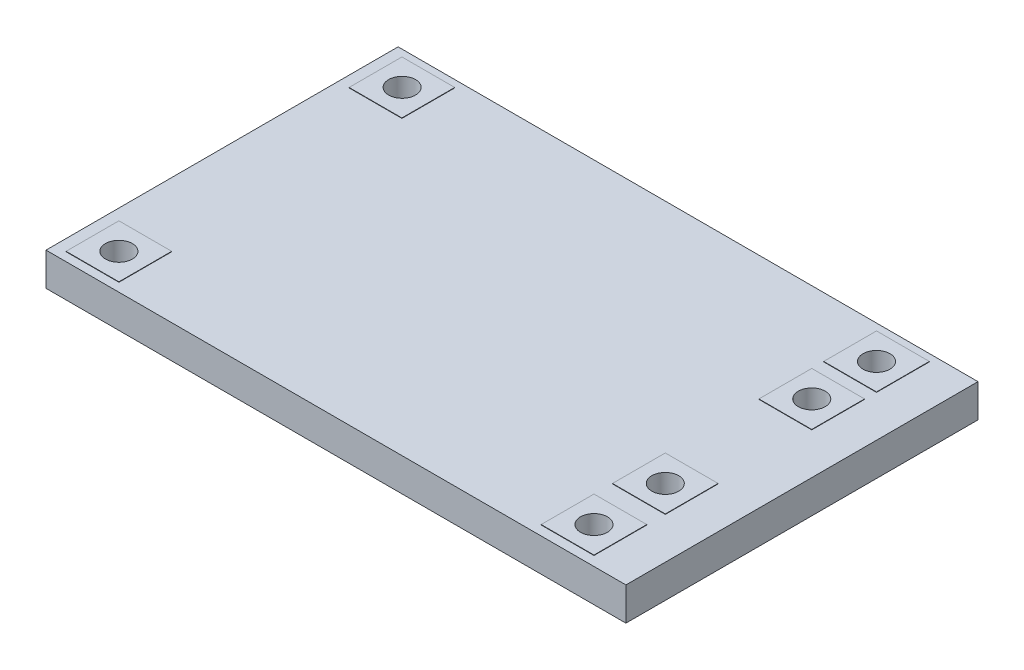
SolidWorks part; units mm, degrees
ref_plane "Front Plane" through (0, 0, 0) normal (0, 0, 1) x (1, 0, 0)
ref_plane "Top Plane" through (0, 0, 0) normal (0, 1, 0) x (1, 0, 0)
ref_plane "Right Plane" through (0, 0, 0) normal (1, 0, 0) x (0, 0, -1)
sketch "Sketch1" plane through (0, 0, 0) normal (0, 1, 0) x (1, 0, 0)
  line L0 (113.0265, 236.9079) -> (141.0265, 236.9079) construction
  line L1 (136.3804, 236.6517) -> (138.9304, 236.6517)
  line L2 (112.9304, 220.0017) -> (140.9304, 220.0017)
  line L3 (112.9304, 220.0017) -> (112.9304, 237.0017)
  line L4 (112.9304, 237.0017) -> (140.9304, 237.0017)
  line L5 (140.9304, 220.0017) -> (140.9304, 237.0017)
  line L6 (113.466, 236.6505) -> (116.016, 236.6505)
  line L7 (113.466, 236.6505) -> (113.466, 234.1005)
  line L8 (113.466, 234.1005) -> (116.016, 234.1005)
  line L9 (116.016, 236.6505) -> (116.016, 234.1005)
  line L10 (136.3804, 236.6517) -> (136.3804, 234.1017)
  line L11 (136.3804, 234.1017) -> (138.9304, 234.1017)
  line L12 (138.9304, 236.6517) -> (138.9304, 234.1017)
  line L13 (136.3846, 233.5201) -> (138.9346, 233.5201)
  line L14 (136.3846, 233.5201) -> (136.3846, 230.9701)
  line L15 (136.3846, 230.9701) -> (138.9346, 230.9701)
  line L16 (138.9346, 233.5201) -> (138.9346, 230.9701)
  line L17 (136.3832, 226.4506) -> (138.9332, 226.4506)
  line L18 (136.3832, 226.4506) -> (136.3832, 223.9006)
  line L19 (136.3832, 223.9006) -> (138.9332, 223.9006)
  line L20 (138.9332, 226.4506) -> (138.9332, 223.9006)
  line L21 (136.3796, 223.0107) -> (138.9296, 223.0107)
  line L22 (136.3796, 223.0107) -> (136.3796, 220.4607)
  line L23 (136.3796, 220.4607) -> (138.9296, 220.4607)
  line L24 (138.9296, 223.0107) -> (138.9296, 220.4607)
  line L25 (113.4856, 222.9666) -> (116.0356, 222.9666)
  line L26 (113.4856, 222.9666) -> (113.4856, 220.4166)
  line L27 (113.4856, 220.4166) -> (116.0356, 220.4166)
  line L28 (116.0356, 222.9666) -> (116.0356, 220.4166)
  circle A0 centre (114.741, 235.3847) radius 0.65
  circle A1 centre (137.6554, 235.3767) radius 0.65
  circle A2 centre (137.6596, 232.2451) radius 0.65
  circle A3 centre (137.6582, 225.1756) radius 0.65
  circle A4 centre (137.6546, 221.7357) radius 0.65
  circle A5 centre (114.7606, 221.6916) radius 0.65
  point P12 (0, 0)
  dimension "D6" = 1.3
  dimension "D7" = 1.275
  dimension "D1" = 28
  dimension "D2" = 28
  dimension "D3" = 17
  dimension "D4" = 2.55
  dimension "D5" = 1.275
  dimension "D8" = 2
  dimension "D9" = 0.35
extrude "Boss-Extrude2" add sketch "Sketch1" along normal blind 1.6 contours L2 L5 L4 L3 L6 L9 L8 L7 L1 L12 L11 L10 L13 L16 L15 L14 L17 L20 L19 L18 L21 L24 L23 L22 L25 L28 L27 L26 region at (126.6544, 0, -228.4929)
extrude "Boss-Extrude3" add sketch "Sketch1<4>" along normal blind 1.62 contours L20 L17 L18 L19 A3 | L16 L13 L14 L15 A2 | L12 L1 L10 L11 A1 | L9 L6 L7 L8 A0 | L28 L25 L26 L27 A5 | L24 L21 L22 L23 A4 region at (137.6554, 0, -236.6156) region at (114.741, 0, -236.6145) region at (137.6596, 0, -233.484) region at (137.6582, 0, -226.4145) region at (137.6546, 0, -222.9746) region at (114.7606, 0, -222.9305)
sketch "Sketch1<4>" plane through (0, 0, 0) normal (0, 1, 0) x (1, 0, 0) same geometry as "Sketch1"
